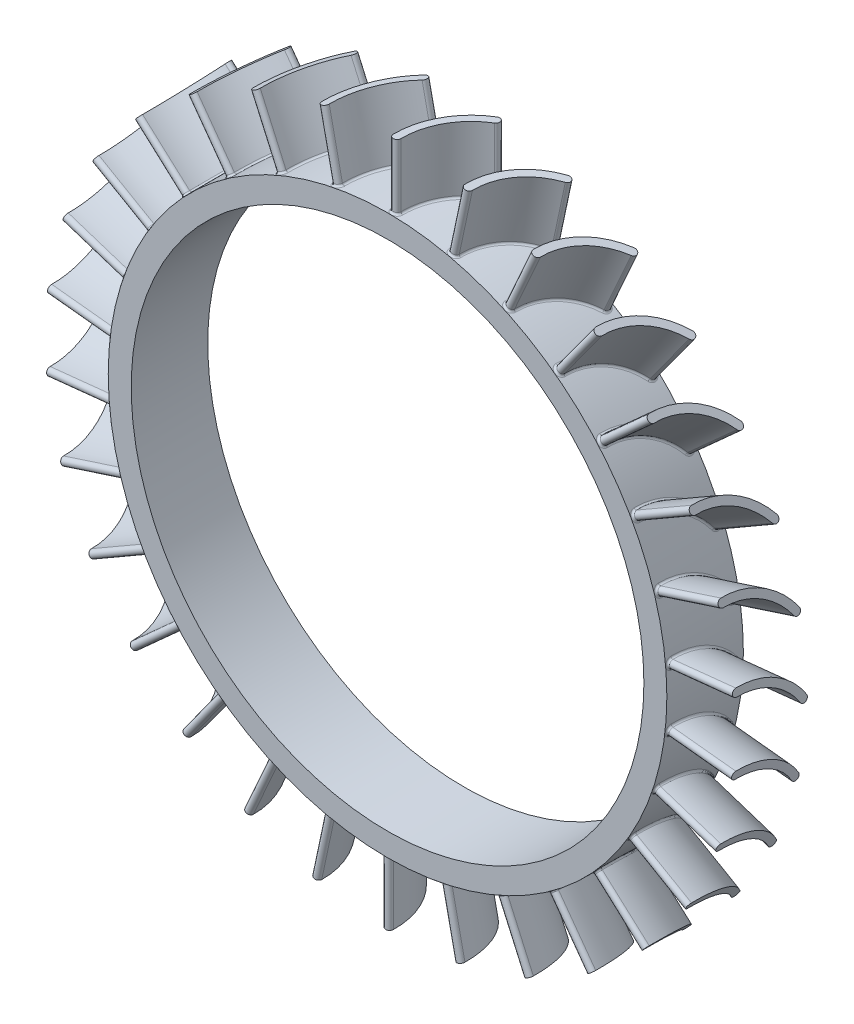
SolidWorks part; units mm, degrees
ref_plane "Front Plane" through (0, 0, 0) normal (0, 0, 1) x (1, 0, 0)
ref_plane "Top Plane" through (0, 0, 0) normal (0, 1, 0) x (1, 0, 0)
ref_plane "Right Plane" through (0, 0, 0) normal (1, 0, 0) x (0, 0, -1)
sketch "Sketch1" plane through (0, 0, 0) normal (0, 0, 1) x (1, 0, 0)
  circle A0 centre (0, 0) radius 73
  circle A1 centre (0, 0) radius 67
  dimension "D1" = 134
  dimension "D2" = 146
extrude "Boss-Extrude1" add sketch "Sketch1" along normal mid plane 20
sketch "Sketch2" plane through (0, 0, 0) normal (0, 1, 0) x (1, 0, 0)
  line L0 (-73, -10) -> (73, -10) construction
  line L1 (67, 10) -> (-67, 10) construction
  arc A0 (-0.0154, -8.5) -> (9.6648, 9) centre (19.9812, -8.1339) cw
  arc A1 (1.9843, -8.4634) -> (10.6964, 7.2866) centre (19.9812, -8.1339) cw
  arc A3 (-0.0154, -8.5) -> (1.9843, -8.4634) centre (0.9844, -8.4817) ccw
  arc A4 (9.6648, 9) -> (10.6964, 7.2866) centre (10.1806, 8.1433) cw
  dimension "D3" = 20
  dimension "D1" = 1.5
  dimension "D2" = 1
  dimension "D4" = 2
extrude "Boss-Extrude2" add sketch "Sketch2" along normal blind 22 from offset 68
fillet "Fillet1" radius 0.5 4 edges at (0.8792, 72.9947, 9.4761) (1.2928, 72.9886, 1.0105) (9.2833, 72.4073, -7.7018) (2.4685, 72.9583, 3.9741)
pattern_circular "CirPattern1" count 30 over 360 about axis through (0, 0, 10) along (0, 0, -1) of "Boss-Extrude2", "Fillet1"
